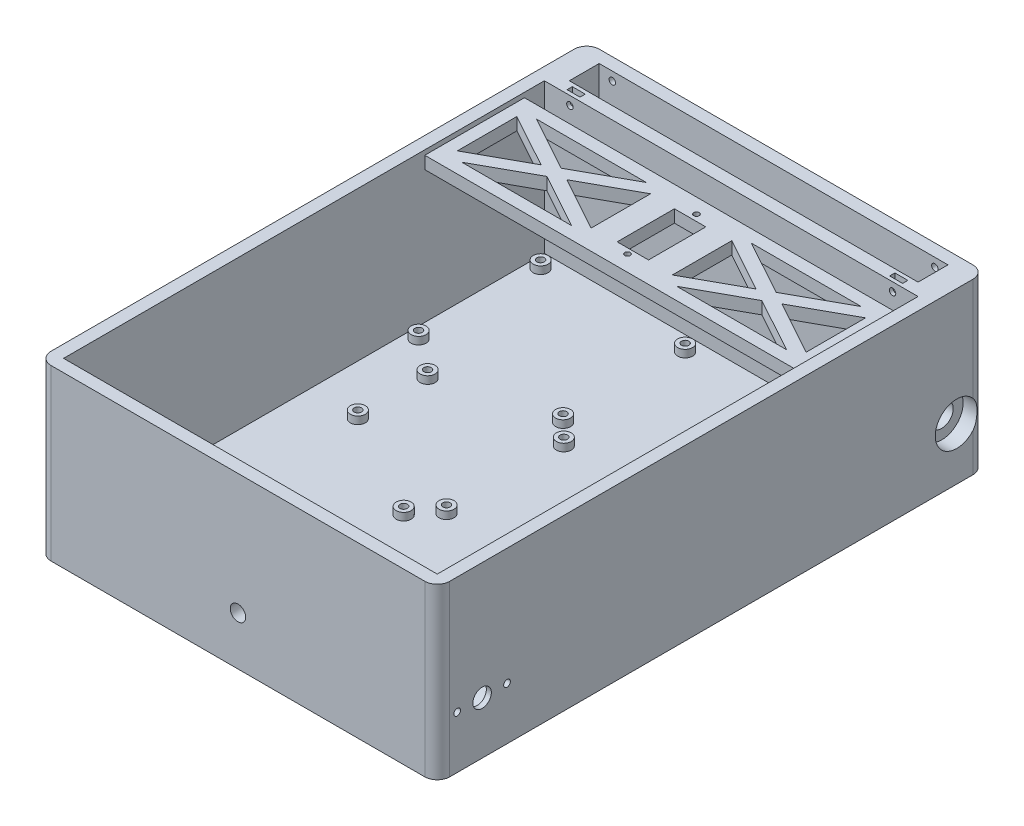
SolidWorks part; units mm, degrees
ref_plane "Front Plane" through (0, 0, 0) normal (0, 0, 1) x (1, 0, 0)
ref_plane "Top Plane" through (0, 0, 0) normal (0, 1, 0) x (1, 0, 0)
ref_plane "Right Plane" through (0, 0, 0) normal (1, 0, 0) x (0, 0, -1)
sketch "Main Body" plane through (0, 0, 0) normal (0, 1, 0) x (1, 0, 0)
  line L0 (-75, 110) -> (75, 110)
  line L1 (-75, -105) -> (75, -105)
  line L2 (-75, -105) -> (-75, 105)
  line L3 (-75, 105) -> (75, 105)
  line L4 (75, -105) -> (75, 105)
  line L5 (-75, -105) -> (75, 105) construction
  line L6 (-75, 105) -> (75, -105) construction
  line L7 (80, -105) -> (80, 105)
  line L8 (-75, -110) -> (75, -110)
  line L9 (-80, -105) -> (-80, 105)
  line L10 (-80, -110) -> (80, -110) construction
  line L11 (-80, -110) -> (-80, 110) construction
  line L12 (80, -110) -> (80, 110) construction
  line L13 (-80, 110) -> (80, 110) construction
  arc A0 (-75, -110) -> (-80, -105) centre (-75, -105) cw
  arc A1 (80, -105) -> (75, -110) centre (75, -105) cw
  arc A2 (75, 110) -> (80, 105) centre (75, 105) cw
  arc A3 (-75, 110) -> (-80, 105) centre (-75, 105) ccw
  point P0 (0, 0)
  dimension "D4" = 5
  dimension "D1" = 75
  dimension "D2" = 210
  dimension "D3" = 5
extrude "Boss-Extrude1" add sketch "Main Body" along normal blind 8 contours L1 L4 L3 L2 | L9 L8 L7 L0 L4 L1 L2 L3 region at (0, 0, -107.2797) region at (0, 0, 0)
extrude "Boss-Extrude3" add sketch "Main Body<4>" along normal blind 60 from surface starting at face at (0, 8, 0)
sketch "Main Body<4>" plane through (0, 0, 0) normal (0, 1, 0) x (1, 0, 0) same geometry as "Main Body"
sketch "Sketch1" plane through (75, 0, 0) normal (-1, 0, 0) x (0, 0, 1)
  line L0 (105, 68) -> (105, 8) construction
  line L1 (-105, 8) -> (105, 8) construction
  line L2 (79, 15.5) -> (105, 15.5)
  line L3 (79, 8) -> (105, 8)
  line L4 (79, 8) -> (79, 34)
  line L5 (79, 34) -> (105, 34)
  line L6 (105, 8) -> (105, 34)
  line L7 (79, 8) -> (105, 34) construction
  line L8 (79, 34) -> (105, 8) construction
  circle A0 centre (92, 21) radius 13
  line M2 (-105, 8) -> (105, 8)
  line M3 (105, 8) -> (105, 68)
  dimension "D1" = 26
  dimension "D2" = 7.5
extrude "Boss-Extrude4" add sketch "Sketch1" along normal up to surface (150 mm away) contours A0 L4 M2 | A0 L3 M3 region at (75, 10.5201, 82.0674) region at (75, 10.5201, 101.9326) up to face at (-75, 38, 0)
sketch "Sketch2" plane through (0, 0, 0) normal (1, 0, 0) x (0, 0, -1)
  line L0 (-105, 68) -> (-105, 15.5) construction
  line L1 (-105, 8) -> (-79, 8)
  line L2 (-105, 8) -> (-105, 15.5)
  line L3 (-105, 15.5) -> (-79, 15.5)
  line L4 (-79, 8) -> (-79, 15.5)
  line L5 (105, 8) -> (-79, 8) construction
  line L6 (-79, 8) -> (-79, 15.5) construction
  line L7 (-79, 15.5) -> (-80.2208, 15.5) construction
extrude "Cut-Extrude1" cut sketch "Sketch2" against normal mid plane 12
sketch "Sketch3" plane through (0, 8, 0) normal (0, 1, 0) x (1, 0, 0)
  line L0 (75, -105) -> (-75, -105) construction
  line L1 (-4, -79) -> (-11, -79)
  line L2 (-4, -79) -> (-4, -105)
  line L3 (-4, -105) -> (-11, -105)
  line L4 (-11, -79) -> (-11, -105)
  line L5 (0, 0) -> (0, -105) construction
  line L6 (-75, -79) -> (-6, -79) construction
  line L7 (11, -79) -> (11, -105)
  line L8 (4, -105) -> (11, -105)
  line L9 (4, -79) -> (4, -105)
  line L10 (4, -79) -> (11, -79)
  line L11 (-6, -103.7792) -> (-6, -92) construction
  dimension "D1" = 5
  dimension "D2" = 4
extrude "Boss-Extrude5" add sketch "Sketch3" along normal blind 20
sketch "Sketch4" plane through (0, 8, 0) normal (0, 1, 0) x (1, 0, 0)
  line L0 (-75, -105) -> (-75, 105) construction
  line L1 (-75, 93) -> (75, 93)
  line L2 (-75, 93) -> (-75, 88)
  line L3 (-75, 88) -> (75, 88)
  line L4 (75, 93) -> (75, 88)
  line L5 (75, 105) -> (75, -105) construction
  line L6 (-75, 105) -> (75, 105) construction
  dimension "D1" = 17
  dimension "D2" = 5
extrude "Boss-Extrude6" add sketch "Sketch4" along normal up to surface (60 mm away) up to face at (0, 68, 0)
sketch "Sketch5" plane through (80, 0, 0) normal (1, 0, 0) x (0, 0, -1)
  circle A0 centre (-92, 21) radius 3.5 construction
  circle A1 centre (-92, 21) radius 3.5
  circle A2 centre (-92, 21) radius 3.7
  dimension "D1" = 0.2
extrude "Cut-Extrude4" cut sketch "Sketch5" against normal up to next contours A1 | A2 A1 region at (80, 21, 92) region at (80, 21, 95.5953)
sketch "Sketch6" plane through (-75, 0, 0) normal (1, 0, 0) x (0, 0, -1)
  circle A0 centre (-92, 21) radius 13
  dimension "D1" = 26
extrude "Cut-Extrude5" cut sketch "Sketch6" against normal offset from surface (3 mm away) 2 up to face at (-80, 34, 0)
mirror "Mirror1" about plane through (0, 0, 0) normal (1, 0, 0) of "Cut-Extrude4"
sketch "Sketch8" plane through (75, 0, 0) normal (-1, 0, 0) x (0, 0, 1)
  circle A0 centre (92, 21) radius 13
  dimension "D1" = 26
extrude "Cut-Extrude6" cut sketch "Sketch8" against normal offset from surface (3 mm away) 2 up to face at (80, 21, 88.3)
sketch "Sketch10" plane through (80, 0, 0) normal (1, 0, 0) x (0, 0, -1)
  circle A1 centre (-82, 21) radius 1.25
  circle A2 centre (-82, 21) radius 1.25
  circle A3 centre (-102, 21) radius 1.25
  circle A4 centre (-102, 21) radius 1.25
  circle A5 centre (-92, 21) radius 12.5
  circle A6 centre (-92, 21) radius 12.5
  circle A63 centre (-102, 21) radius 1.35
  circle A64 centre (-82, 21) radius 1.35
  dimension "D1" = 0
  dimension "D2" = 0
  dimension "D3" = 0
  dimension "D4" = 0.1
  dimension "D5" = 0.1
extrude "Cut-Extrude7" cut sketch "Sketch10" against normal up to next contours A2 | A64 A2 | A4 | A63 A4 region at (80, 21, 82) region at (80, 21, 102) region at (80, 21, 103.3118) region at (80, 21, 83.3118)
mirror "Mirror3" about plane through (0, 0, 0) normal (1, 0, 0) of "Cut-Extrude7"
sketch "Sketch11" plane through (80, 0, 0) normal (1, 0, 0) x (0, 0, -1)
  circle A0 centre (98.5, 21) radius 4.5 construction
  circle A1 centre (98.5, 21) radius 4.5
  circle A3 centre (98.5, 21) radius 4.6
  dimension "D1" = 0.1
extrude "Cut-Extrude10" cut sketch "Sketch11" against normal through all contours A1 | A3 A1 region at (80, 21, -98.5) region at (80, 21, -93.913)
sketch "Sketch12" plane through (-75, 0, 0) normal (1, 0, 0) x (0, 0, -1)
  line L0 (93, 8) -> (105, 8) construction
  line L1 (93, 68) -> (105, 68)
  line L2 (93, 68) -> (93, 8)
  line L3 (93, 8) -> (105, 8)
  line L4 (105, 68) -> (105, 8)
  line L6 (93, 68) -> (93, 8) construction
  line L7 (93, 68) -> (105, 68) construction
  circle A2 centre (98.5, 21) radius 4.6 construction
  circle A3 centre (98.5, 21) radius 4.6
extrude "Boss-Extrude7" add sketch "Sketch12" along normal blind 5
sketch "Sketch13" plane through (-80, 0, 0) normal (-1, 0, 0) x (0, 0, 1)
  circle A0 centre (-98.5, 21) radius 8.6
  circle A2 centre (-98.5, 21) radius 4.6 construction
  dimension "D1" = 17.2
extrude "Cut-Extrude11" cut sketch "Sketch13" against normal blind 6
mirror "Mirror4" about plane through (0, 0, 0) normal (1, 0, 0) of "Boss-Extrude7", "Cut-Extrude11"
sketch "Sketch14" plane through (0, 8, 0) normal (0, 1, 0) x (1, 0, 0)
  line L0 (-4, -105) -> (-4, -79) construction
  line L1 (-4, -95) -> (4, -95)
  line L2 (-4, -95) -> (-4, -105)
  line L3 (-4, -105) -> (4, -105)
  line L4 (4, -95) -> (4, -105)
  dimension "D1" = 10
extrude "Boss-Extrude9" add sketch "Sketch14" along normal blind 5
sketch "Sketch15" plane through (0, 0, 110) normal (0, 0, 1) x (1, 0, 0)
  arc A0 (-3, 19.5) -> (3, 19.5) centre (0, 19.5) ccw construction
  arc A1 (-3, 19.5) -> (3, 19.5) centre (0, 19.5) ccw
  arc A2 (3, 19.5) -> (-3, 19.5) centre (0, 19.5) ccw construction
  arc A3 (3, 19.5) -> (-3, 19.5) centre (0, 19.5) ccw
  arc A4 (3.1, 19.5) -> (-3.1, 19.5) centre (0, 19.5) ccw
  arc A5 (-3.1, 19.5) -> (3.1, 19.5) centre (0, 19.5) ccw
  dimension "D1" = 0.1
extrude "Cut-Extrude12" cut sketch "Sketch15" against normal up to next contours A1 A3 | A4 A5 A3 A1 region at (0, 19.5, 110) region at (0, 16.4877, 110)
sketch "Sketch16" plane through (0, 0, 0) normal (0, -1, 0) x (1, 0, 0)
  circle A0 centre (-12.5, -82) radius 1.475 construction
  circle A1 centre (-70.5, -82) radius 1.475 construction
  circle A2 centre (-70.5, -33) radius 1.475 construction
  circle A3 centre (-12.5, -33) radius 1.475 construction
  circle A4 centre (-4.2, -25) radius 1.475 construction
  circle A5 centre (-55, -21.12) radius 1.475 construction
  circle A6 centre (-55, 6.88) radius 1.475 construction
  circle A7 centre (-4.2, 22.08) radius 1.475 construction
  circle A8 centre (-12.3, 31.18) radius 1.475 construction
  circle A9 centre (24.2, 31.18) radius 1.475 construction
  circle A10 centre (37.8459, 24.117) radius 1.475 construction
  circle A11 centre (59.5541, 24.117) radius 1.475 construction
  circle A12 centre (59.5541, 68.243) radius 1.475 construction
  circle A13 centre (37.8459, 68.243) radius 1.475 construction
  circle A14 centre (24.2, 67.68) radius 1.475 construction
  circle A15 centre (-12.3, 67.68) radius 1.475 construction
  circle A16 centre (-12.5, -82) radius 1.475
  circle A17 centre (-70.5, -82) radius 1.475
  circle A18 centre (-70.5, -33) radius 1.475
  circle A19 centre (-12.5, -33) radius 1.475
  circle A20 centre (-4.2, -25) radius 1.475
  circle A21 centre (-55, -21.12) radius 1.475
  circle A22 centre (-55, 6.88) radius 1.475
  circle A23 centre (-4.2, 22.08) radius 1.475
  circle A24 centre (-12.3, 31.18) radius 1.475
  circle A25 centre (24.2, 31.18) radius 1.475
  circle A26 centre (37.8459, 24.117) radius 1.475
  circle A27 centre (59.5541, 24.117) radius 1.475
  circle A28 centre (59.5541, 68.243) radius 1.475
  circle A29 centre (37.8459, 68.243) radius 1.475
  circle A30 centre (24.2, 67.68) radius 1.475
  circle A31 centre (-12.3, 67.68) radius 1.475
extrude "Cut-Extrude13" cut sketch "Sketch16" against normal up to next
sketch "Sketch17" plane through (0, 8, 0) normal (0, 1, 0) x (1, 0, 0)
  line L0 (0, 88) -> (0, -110) construction
  line L1 (-75, 88) -> (75, 88) construction
  line L2 (75, -110) -> (-75, -110) construction
  line L3 (-75, 4.5) -> (75, 4.5) construction
  line L7 (-75, -79) -> (-75, 88) construction
  line L8 (75, 88) -> (75, -79) construction
  circle A0 centre (-70.5, 82) radius 3
  circle A1 centre (-12.5, 82) radius 3
  circle A2 centre (-12.3, -67.68) radius 1.475
  circle A3 centre (-12.3, -67.68) radius 1.475
  circle A4 centre (24.2, -67.68) radius 1.475
  circle A5 centre (24.2, -67.68) radius 1.475
  circle A6 centre (37.8459, -68.243) radius 1.475
  circle A7 centre (37.8459, -68.243) radius 1.475
  circle A8 centre (59.5541, -68.243) radius 1.475
  circle A9 centre (59.5541, -68.243) radius 1.475
  circle A10 centre (59.5541, -24.117) radius 1.475
  circle A11 centre (59.5541, -24.117) radius 1.475
  circle A12 centre (37.8459, -24.117) radius 1.475
  circle A13 centre (37.8459, -24.117) radius 1.475
  circle A14 centre (24.2, -31.18) radius 1.475
  circle A15 centre (24.2, -31.18) radius 1.475
  circle A16 centre (-12.3, -31.18) radius 1.475
  circle A17 centre (-12.3, -31.18) radius 1.475
  circle A18 centre (-4.2, -22.08) radius 1.475
  circle A19 centre (-4.2, -22.08) radius 1.475
  circle A20 centre (-55, -6.88) radius 1.475
  circle A21 centre (-55, -6.88) radius 1.475
  circle A22 centre (-55, 21.12) radius 1.475
  circle A23 centre (-55, 21.12) radius 1.475
  circle A24 centre (-4.2, 25) radius 1.475
  circle A25 centre (-4.2, 25) radius 1.475
  circle A26 centre (-12.5, 33) radius 1.475
  circle A27 centre (-12.5, 33) radius 1.475
  circle A28 centre (-70.5, 33) radius 1.475
  circle A29 centre (-70.5, 33) radius 1.475
  circle A30 centre (-70.5, 82) radius 1.475
  circle A31 centre (-70.5, 82) radius 1.475
  circle A32 centre (-12.5, 82) radius 1.475
  circle A33 centre (-12.5, 82) radius 1.475
  circle A34 centre (-70.5, 33) radius 3
  circle A35 centre (-55, 21.12) radius 3
  circle A36 centre (-12.5, 33) radius 3
  circle A37 centre (-4.2, 25) radius 3
  circle A38 centre (-55, -6.88) radius 3
  circle A39 centre (-4.2, -22.08) radius 3
  circle A40 centre (-12.3, -31.18) radius 3
  circle A41 centre (24.2, -31.18) radius 3
  circle A42 centre (37.8459, -24.117) radius 3
  circle A43 centre (59.5541, -24.117) radius 3
  circle A44 centre (-12.3, -67.68) radius 3
  circle A45 centre (24.2, -67.68) radius 3
  circle A46 centre (37.8459, -68.243) radius 3
  circle A47 centre (59.5541, -68.243) radius 3
  dimension "D1" = 6
  dimension "D2" = 0
  dimension "D3" = 0
  dimension "D4" = 0
  dimension "D5" = 0
  dimension "D6" = 0
  dimension "D7" = 0
  dimension "D8" = 0
  dimension "D9" = 0
  dimension "D10" = 0
  dimension "D11" = 0
  dimension "D12" = 0
  dimension "D13" = 0
  dimension "D14" = 0
  dimension "D15" = 0
  dimension "D16" = 0
  dimension "D17" = 0
extrude "Boss-Extrude10" add sketch "Sketch17" along normal blind 3
sketch "Sketch18" plane through (75, 0, 0) normal (-1, 0, 0) x (0, 0, 1)
  line L1 (-80, 66.1) -> (-40, 66.1)
  line L2 (-80, 66.1) -> (-80, 61.1)
  line L3 (-80, 61.1) -> (-40, 61.1)
  line L4 (-40, 66.1) -> (-40, 61.1)
  line L5 (-88, 68) -> (105, 68) construction
  point P4 (-80.7351, 61.3996)
  dimension "D1" = 5
  dimension "D2" = 30
  dimension "D3" = 40
  dimension "D4" = 1.9
extrude "Boss-Extrude11" add sketch "Sketch18" along normal up to next
sketch "Sketch19" plane through (0, 68, 0) normal (0, 1, 0) x (1, 0, 0)
  line L1 (-6.3, 71.5) -> (6.3, 71.5)
  line L2 (-6.3, 71.5) -> (-6.3, 48.5)
  line L3 (-6.3, 48.5) -> (6.3, 48.5)
  line L4 (6.3, 71.5) -> (6.3, 48.5)
  line L12 (-75, 80) -> (-75, 40)
  line L13 (-75, 40) -> (75, 40)
  line L14 (75, 40) -> (75, 80)
  line L15 (75, 80) -> (-75, 80)
  line L16 (-75, 80) -> (-75, 40)
  line L17 (-75, 40) -> (75, 40)
  line L18 (75, 40) -> (75, 80)
  line L19 (75, 80) -> (-75, 80)
  point P4 (0, 71.5)
  point P8 (0, 80)
  point P12 (6.3, 60)
  point P13 (75, 60)
  point P14 (13.8858, 70.0042)
  point P15 (0, 0)
  point P16 (0, 0)
  point P17 (0, 0)
  dimension "D1" = 23
  dimension "D2" = 12.6
  dimension "D3" = 0
extrude "Cut-Extrude14" cut sketch "Sketch19" against normal up to next contours L4 L1 L2 L3 region at (0, 68, -60)
sketch "Sketch21" plane through (0, 0, -110) normal (0, 0, -1) x (-1, 0, 0)
  circle A1 centre (-64.75, 64.5) radius 1.3
  circle A2 centre (-64.75, 64.5) radius 1.3
  circle A3 centre (64.75, 64.5) radius 1.3
  circle A4 centre (64.75, 64.5) radius 1.3
  dimension "D1" = 0
  dimension "D2" = 0
extrude "Cut-Extrude16" cut sketch "Sketch21" against normal up to surface (22 mm away) up to face at (0, 38, -88)
ref_plane "Plane1" through (0, 0, -90.5) normal (0, 0, -1) x (-1, 0, 0)
sketch "Sketch22" plane through (0, 0, -90.5) normal (0, 0, -1) x (-1, 0, 0)
  line L0 (-67.35, 66.0011) -> (-67.35, 68)
  line L1 (-62.15, 66.0011) -> (-64.75, 67.5022)
  line L2 (-64.75, 67.5022) -> (-67.35, 66.0011)
  line L3 (-67.35, 66.0011) -> (-67.35, 62.9989)
  line L4 (-67.35, 62.9989) -> (-64.75, 61.4978)
  line L5 (-64.75, 61.4978) -> (-62.15, 62.9989)
  line L6 (-62.15, 62.9989) -> (-62.15, 66.0011)
  line L7 (-67.35, 68) -> (-62.15, 68)
  line L8 (-62.15, 68) -> (-62.15, 66.0011)
  line L9 (70, 68) -> (-70, 68) construction
  line L10 (0, 0) -> (0, 68) construction
  line L11 (75, 68) -> (-75, 68) construction
  line L12 (64.75, 61.4978) -> (62.15, 62.9989)
  line L13 (67.35, 62.9989) -> (64.75, 61.4978)
  line L14 (64.75, 67.5022) -> (67.35, 66.0011)
  line L15 (67.35, 66.0011) -> (67.35, 62.9989)
  line L16 (67.35, 66.0011) -> (67.35, 68)
  line L17 (62.15, 62.9989) -> (62.15, 66.0011)
  line L18 (62.15, 68) -> (62.15, 66.0011)
  line L19 (67.35, 68) -> (62.15, 68)
  line L20 (62.15, 66.0011) -> (64.75, 67.5022)
  circle A0 centre (-64.75, 64.5) radius 2.6 construction
  point P16 (0, 0)
  dimension "D1" = 5.2
extrude "Cut-Extrude17" cut sketch "Sketch22" against normal mid plane 2.1 contours L20 L17 L12 L13 L15 L14 | L18 L20 L14 L16 L19 | L5 L6 L1 L2 L3 L4 | L8 L7 L0 L2 L1 region at (67.2943, 67.0006, -90.5) region at (64.75, 64.5, -90.5) region at (-64.75, 64.5, -90.5) region at (-62.2057, 67.0006, -90.5)
sketch "Sketch23" plane through (0, 0, -110) normal (0, 0, -1) x (-1, 0, 0)
  circle A0 centre (64.75, 64.5) radius 2.5
  circle A1 centre (-64.75, 64.5) radius 2.5
  dimension "D1" = 5
  dimension "D2" = 5
extrude "Cut-Extrude18" cut sketch "Sketch23" against normal mid plane 2.5
sketch "Sketch24" plane through (0, 66.1, 0) normal (0, 1, 0) x (1, 0, 0)
  circle A0 centre (0, 46.35) radius 1.1002
  arc A1 (0.4, 45.4333) -> (-0.4, 45.4333) centre (0, 46.35) ccw construction
  circle A2 centre (0, 74.05) radius 1.1002
  arc A3 (-0.4, 74.9667) -> (0, 73.0498) centre (0, 74.05) ccw construction
  point P5 (0.4, 45.4333)
  dimension "D1" = 0.1
extrude "Cut-Extrude19" cut sketch "Sketch24" against normal up to next
sketch "Sketch25" plane through (0, 66.1, 0) normal (0, 1, 0) x (1, 0, 0)
  line L0 (6.3, 71.5) -> (6.3, 48.5) construction
  line L1 (-11.3, 80) -> (11.3, 80)
  line L2 (-11.3, 80) -> (-11.3, 40)
  line L3 (-11.3, 40) -> (11.3, 40)
  line L4 (-75, 80) -> (-75, 40)
  line L5 (-75, 40) -> (75, 40)
  line L6 (75, 40) -> (75, 80)
  line L7 (75, 80) -> (-75, 80)
  line L8 (-75, 80) -> (-75, 40)
  line L9 (-75, 40) -> (75, 40)
  line L10 (75, 40) -> (75, 80)
  line L11 (75, 80) -> (-75, 80)
  line L12 (11.3, 80) -> (11.3, 40)
  line L13 (-11.3, 80) -> (11.3, 40) construction
  line L14 (-11.3, 40) -> (11.3, 80) construction
  line L15 (0, 80) -> (0, 40) construction
  line L16 (70, 75) -> (70, 45)
  line L17 (-70, 75) -> (-16.3, 75)
  line L18 (-70, 75) -> (-70, 45)
  line L19 (-70, 45) -> (-16.3, 45)
  line L20 (-16.3, 75) -> (-16.3, 45)
  line L21 (-70, 75) -> (-16.3, 45) construction
  line L22 (-70, 45) -> (-16.3, 75) construction
  line L23 (70, 75) -> (16.3, 45) construction
  line L24 (70, 45) -> (16.3, 75) construction
  line L25 (70, 75) -> (16.3, 75)
  line L26 (16.3, 75) -> (16.3, 45)
  line L27 (70, 45) -> (16.3, 45)
  line L28 (-75, 60) -> (-11.3, 60) construction
  line L29 (75, 60) -> (11.3, 60) construction
  line L30 (-70, 71.9362) -> (-48.3314, 60)
  line L31 (-16.3, 71.9362) -> (-37.9686, 60)
  line L32 (70, 71.9362) -> (48.3314, 60)
  line L33 (-48.3314, 60) -> (-70, 48.0638)
  line L34 (48.3314, 60) -> (70, 48.0638)
  line L35 (-65.199, 45) -> (-43.15, 57.1458)
  line L36 (65.199, 45) -> (43.15, 57.1458)
  line L37 (-43.15, 57.1458) -> (-21.101, 45)
  line L38 (43.15, 57.1458) -> (21.101, 45)
  line L39 (16.3, 71.9362) -> (37.9686, 60)
  line L40 (-37.9686, 60) -> (-16.3, 48.0638)
  line L41 (37.9686, 60) -> (16.3, 48.0638)
  line L42 (-65.199, 75) -> (-43.15, 62.8542)
  line L43 (65.199, 75) -> (43.15, 62.8542)
  line L44 (-43.15, 62.8542) -> (-21.101, 75)
  line L45 (43.15, 62.8542) -> (21.101, 75)
  line L46 (-75, 40) -> (-75, 80) construction
  line L47 (-75, 40) -> (75, 40) construction
  point P2 (0, 60)
  point P9 (-43.15, 60)
  point P10 (75, 60)
  point P24 (43.15, 60)
  point P53 (0, 0)
  point P54 (0, 0)
  point P55 (-49.1249, 60)
  point P56 (-49.0952, 60)
  point P57 (-43.15, 61.9207)
  point P58 (0, 0)
  point P59 (0, 0)
  point P60 (-66.7795, 75)
  point P61 (-43.15, 64.6951)
  point P62 (-54.1745, 68.9271)
  dimension "D2" = 5
  dimension "D3" = 5
  dimension "D4" = 5
  dimension "D5" = 5
  dimension "D6" = 26.6686
  dimension "D1" = 0
extrude "Cut-Extrude21" cut sketch "Sketch25" against normal up to next contours L37 L35 L19 | L33 L30 L18 | L42 L44 L17 | L31 L40 L20 | L41 L39 L26 | L45 L43 L25 | L36 L38 L27 | L32 L34 L16 region at (62.7771, 66.1, -60) region at (43.15, 66.1, -70.9514) region at (43.15, 66.1, -49.0486) region at (23.5229, 66.1, -60) region at (-43.15, 66.1, -70.9514) region at (-62.7771, 66.1, -60) region at (-23.5229, 66.1, -60) region at (-43.15, 66.1, -49.0486)
